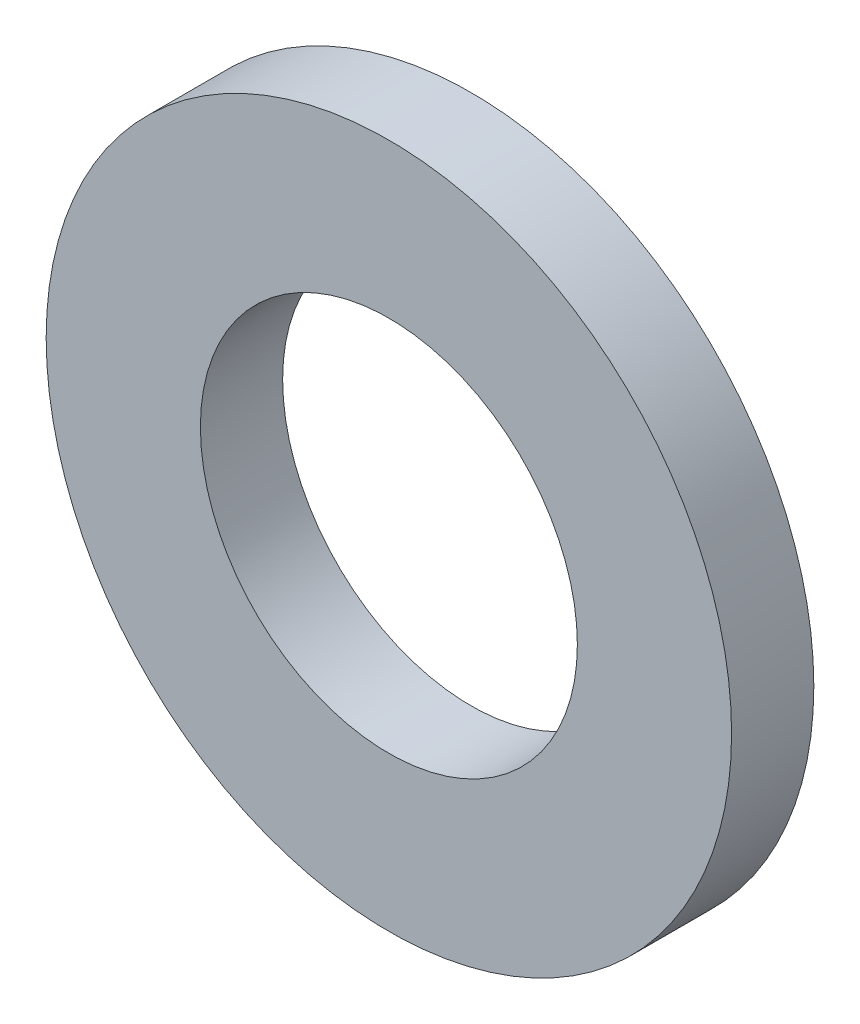
SolidWorks part; units mm, degrees
ref_plane "Front Plane" through (0, 0, 0) normal (0, 0, 1) x (1, 0, 0)
ref_plane "Top Plane" through (0, 0, 0) normal (0, 1, 0) x (1, 0, 0)
ref_plane "Right Plane" through (0, 0, 0) normal (1, 0, 0) x (0, 0, -1)
sketch "Sketch1" plane through (0, 0, 0) normal (0, 0, 1) x (1, 0, 0)
  circle A0 centre (0, 0) radius 5
  circle A1 centre (0, 0) radius 2.75
  dimension "OD" = 10
  dimension "ID1" = 5.5
extrude "Boss-Extrude1" add sketch "Sketch1" along normal blind 1.2
ref_axis "Center Axis 1" through (0, 0, 1.2) along (0, 0, -1)
ref_plane "Contact Plane 1" through (0, 0, 1.2) normal (0, 0, 1) x (1, 0, 0)
ref_plane "Contact Plane 2" through (0, 0, 0) normal (0, 0, -1) x (-1, 0, 0)
